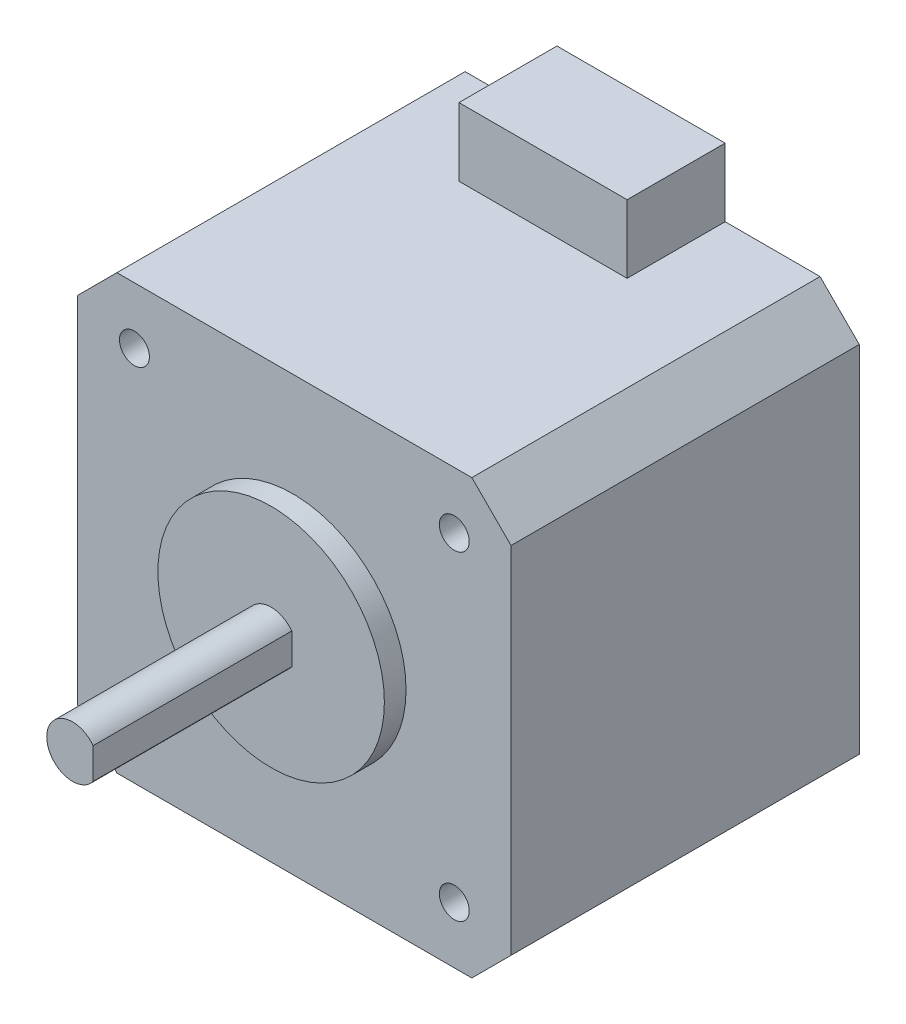
SolidWorks part; units mm, degrees
ref_plane "Front Plane" through (0, 0, 0) normal (0, 0, 1) x (1, 0, 0)
ref_plane "Top Plane" through (0, 0, 0) normal (0, 1, 0) x (1, 0, 0)
ref_plane "Right Plane" through (0, 0, 0) normal (1, 0, 0) x (0, 0, -1)
sketch "Sketch1" plane through (0, 0, 0) normal (0, 0, 1) x (1, 0, 0)
  line L0 (12.7, 42) -> (12.7, 48.6)
  line L1 (3.8, 0) -> (38.2, 0)
  line L2 (0, 3.8) -> (0, 38.2)
  line L3 (3.8, 42) -> (12.7, 42)
  line L4 (42, 3.8) -> (42, 38.2)
  line L5 (12.7, 48.6) -> (29, 48.6)
  line L6 (29, 48.6) -> (29, 42)
  line L7 (29, 42) -> (38.2, 42)
  line L8 (12.7, 42) -> (29, 42)
  line L9 (0, 38.2) -> (3.8, 42)
  line L10 (38.2, 42) -> (42, 38.2)
  line L11 (38.2, 0) -> (42, 3.8)
  line L12 (0, 3.8) -> (3.8, 0)
  point P0 (0, 0)
  point P1 (42, 42)
  point P2 (0, 42)
  point P3 (42, 0)
  dimension "D1" = 42
  dimension "D2" = 42
  dimension "D3" = 13
  dimension "D4" = 16.3
  dimension "D5" = 6.6
extrude "Boss-Extrude1" add sketch "Sketch1" along normal blind 33.75 contours L2 L12 L1 L11 L4 L10 L7 L8 L3 L9 region at (21, 21, 0)
extrude "Boss-Extrude2" add sketch "Sketch1<3>" along normal blind 9.5 contours L0 L8 L6 L5 region at (20.85, 45.3, 0)
sketch "Sketch1<3>" plane through (0, 0, 0) normal (0, 0, 1) x (1, 0, 0) same geometry as "Sketch1"
sketch "Sketch2" plane through (0, 0, 33.75) normal (0, 0, 1) x (1, 0, 0)
  line L0 (20.85, 42) -> (20.85, 17.6573) construction
  line L1 (12.7, 42) -> (29, 42) construction
  line L2 (0, 21) -> (24.1812, 21) construction
  line L3 (0, 3.8) -> (0, 38.2) construction
  circle A0 centre (20.85, 21) radius 10.975
  dimension "D1" = 21.95
extrude "Boss-Extrude3" add sketch "Sketch2" along normal blind 2.1
sketch "Sketch3" plane through (0, 0, 35.85) normal (0, 0, 1) x (1, 0, 0)
  line L0 (22.85, 22.5) -> (22.85, 19.5)
  line L1 (20.85, 21) -> (18.35, 21) construction
  arc A0 (22.85, 22.5) -> (22.85, 19.5) centre (20.85, 21) ccw
  circle A1 centre (20.85, 21) radius 10.975 construction
  dimension "D1" = 0
  dimension "D2" = 5
  dimension "D3" = 4.5
extrude "Boss-Extrude4" add sketch "Sketch3" along normal blind 19.25
sketch "Sketch4" plane through (0, 0, 33.75) normal (0, 0, 1) x (1, 0, 0)
  line L1 (21, 42) -> (21, 38.6427) construction
  line L2 (3.8, 42) -> (38.2, 42) construction
  line L3 (0, 21) -> (4.697, 21) construction
  line L4 (0, 3.8) -> (0, 38.2) construction
  circle A0 centre (5.5, 36.5) radius 1.45
  circle A1 centre (36.5, 36.5) radius 1.45
  circle A2 centre (5.5, 5.5) radius 1.45
  circle A3 centre (36.5, 5.5) radius 1.45
  dimension "D1" = 2.9
  dimension "D2" = 31
  dimension "D3" = 15.5
  dimension "D4" = 31
  dimension "D5" = 15.5
extrude "Cut-Extrude1" cut sketch "Sketch4" against normal blind 4.5
